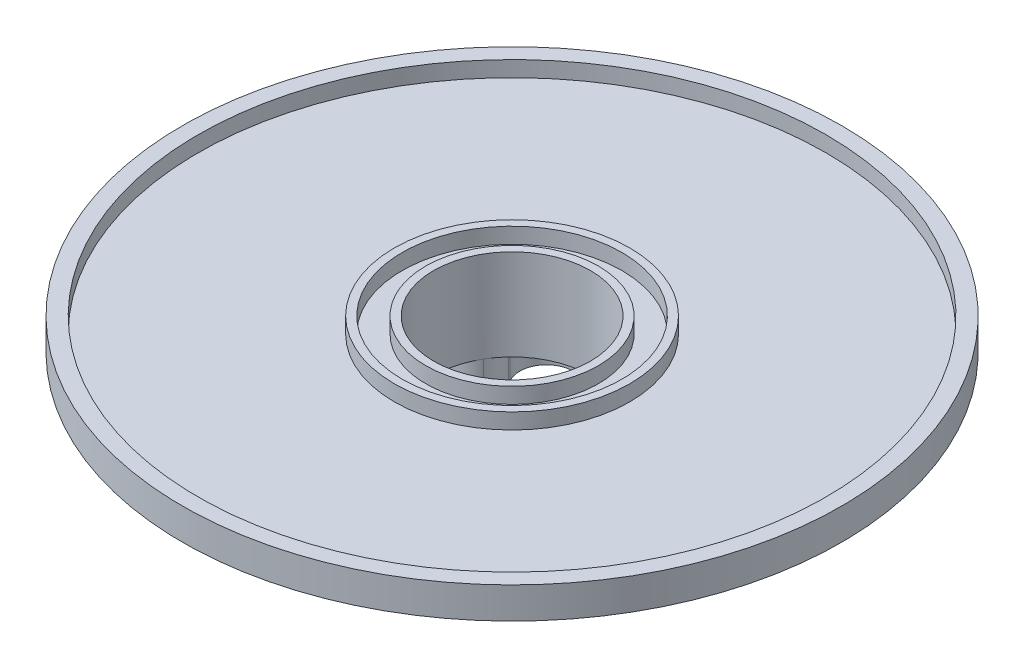
SolidWorks part; units mm, degrees
ref_plane "Front Plane" through (0, 0, 0) normal (0, 0, 1) x (1, 0, 0)
ref_plane "Top Plane" through (0, 0, 0) normal (0, 1, 0) x (1, 0, 0)
ref_plane "Right Plane" through (0, 0, 0) normal (1, 0, 0) x (0, 0, -1)
sketch "Sketch1" plane through (0, 0, 0) normal (0, 0, 1) x (1, 0, 0)
  line L0 (0, 0) -> (0, 80) construction
  line L1 (0, 0) -> (-50, 0)
  line L2 (-50, 0) -> (-50, 30)
  line L3 (-50, 30) -> (-105, 30)
  line L4 (-105, 30) -> (-105, 40)
  line L5 (-105, 40) -> (-100, 40)
  line L6 (-100, 40) -> (-100, 35)
  line L7 (-100, 35) -> (0, 35)
  line L8 (0, 0) -> (0, 35)
  dimension "D1" = 50
  dimension "D2" = 30
  dimension "D3" = 10
  dimension "D4" = 100
  dimension "D5" = 5
  dimension "D6" = 5
revolve "Revolve1" add sketch "Sketch1" angle 360 about L0
sketch "Sketch2" plane through (0, 0, 0) normal (0, -1, 0) x (1, 0, 0)
  line L0 (0, 0) -> (-30, 0) construction
  line L1 (-30, -7.5) -> (-22.798, -7.5) construction
  line L2 (-8.5048, 29.7308) -> (-4.9038, 23.4937) construction
  line L3 (-30, 7.5) -> (-22.798, 7.5) construction
  line L4 (-21.4952, 22.2308) -> (-17.8942, 15.9937) construction
  line L5 (21.4952, 22.2308) -> (17.8942, 15.9937) construction
  line L6 (8.5048, 29.7308) -> (4.9038, 23.4937) construction
  line L7 (30, -7.5) -> (22.798, -7.5) construction
  line L8 (30, 7.5) -> (22.798, 7.5) construction
  line L9 (8.5048, -29.7308) -> (4.9038, -23.4937) construction
  line L10 (21.4952, -22.2308) -> (17.8942, -15.9937) construction
  line L11 (-21.4952, -22.2308) -> (-17.8942, -15.9937) construction
  line L12 (-8.5048, -29.7308) -> (-4.9038, -23.4937) construction
  line L13 (0, 0) -> (-22.798, 7.5) construction
  line L14 (-22.3612, 21.7308) -> (-19.1165, 16.1108)
  line L15 (-30, 8.5) -> (-23.5106, 8.5)
  line L16 (-30, -8.5) -> (-23.5106, -8.5)
  line L17 (-22.3612, -21.7308) -> (-19.1165, -16.1108)
  line L18 (-7.6388, -30.2308) -> (-4.3941, -24.6108)
  line L19 (7.6388, -30.2308) -> (4.3941, -24.6108)
  line L20 (22.3612, -21.7308) -> (19.1165, -16.1108)
  line L21 (30, -8.5) -> (23.5106, -8.5)
  line L22 (30, 8.5) -> (23.5106, 8.5)
  line L23 (22.3612, 21.7308) -> (19.1165, 16.1108)
  line L24 (7.6388, 30.2308) -> (4.3941, 24.6108)
  line L25 (-7.6388, 30.2308) -> (-4.3941, 24.6108)
  arc A0 (-22.798, -7.5) -> (-17.8942, -15.9937) centre (0, 0) ccw construction
  arc A1 (-30, 7.5) -> (-30, -7.5) centre (-30, 0) ccw construction
  arc A2 (-8.5048, 29.7308) -> (-21.4952, 22.2308) centre (-15, 25.9808) ccw construction
  arc A3 (21.4952, 22.2308) -> (8.5048, 29.7308) centre (15, 25.9808) ccw construction
  arc A4 (30, -7.5) -> (30, 7.5) centre (30, 0) ccw construction
  arc A5 (8.5048, -29.7308) -> (21.4952, -22.2308) centre (15, -25.9808) ccw construction
  arc A6 (-21.4952, -22.2308) -> (-8.5048, -29.7308) centre (-15, -25.9808) ccw construction
  arc A7 (-17.8942, 15.9937) -> (-22.798, 7.5) centre (0, 0) ccw construction
  arc A8 (4.9038, 23.4937) -> (-4.9038, 23.4937) centre (0, 0) ccw construction
  arc A9 (22.798, 7.5) -> (17.8942, 15.9937) centre (0, 0) ccw construction
  arc A10 (17.8942, -15.9937) -> (22.798, -7.5) centre (0, 0) ccw construction
  arc A11 (-4.9038, -23.4937) -> (4.9038, -23.4937) centre (0, 0) ccw construction
  arc A12 (-7.6388, 30.2308) -> (-22.3612, 21.7308) centre (-15, 25.9808) ccw
  arc A13 (-19.1165, 16.1108) -> (-23.5106, 8.5) centre (0, 0) ccw
  arc A14 (-30, 8.5) -> (-30, -8.5) centre (-30, 0) ccw
  arc A15 (-23.5106, -8.5) -> (-19.1165, -16.1108) centre (0, 0) ccw
  arc A16 (-22.3612, -21.7308) -> (-7.6388, -30.2308) centre (-15, -25.9808) ccw
  arc A17 (-4.3941, -24.6108) -> (4.3941, -24.6108) centre (0, 0) ccw
  arc A18 (7.6388, -30.2308) -> (22.3612, -21.7308) centre (15, -25.9808) ccw
  arc A19 (19.1165, -16.1108) -> (23.5106, -8.5) centre (0, 0) ccw
  arc A20 (30, -8.5) -> (30, 8.5) centre (30, 0) ccw
  arc A21 (23.5106, 8.5) -> (19.1165, 16.1108) centre (0, 0) ccw
  arc A22 (22.3612, 21.7308) -> (7.6388, 30.2308) centre (15, 25.9808) ccw
  arc A23 (4.3941, 24.6108) -> (-4.3941, 24.6108) centre (0, 0) ccw
  dimension "D1" = 1
  dimension "D3" = 15
  dimension "D2" = 30
  dimension "D6" = 18.21
  dimension "D4" = 6
extrude "Cut-Extrude1" cut sketch "Sketch2" against normal blind 11
fillet "Fillet1" radius 8 12 edges at (23.5106, 5.5, -8.5) (19.1165, 5.5, -16.1108) (-4.3941, 5.5, -24.6108) (4.3941, 5.5, -24.6108) (-23.5106, 5.5, -8.5) (-19.1165, 5.5, -16.1108) (19.1165, 5.5, 16.1108) (23.5106, 5.5, 8.5) (4.3941, 5.5, 24.6108) (-4.3941, 5.5, 24.6108) (-23.5106, 5.5, 8.5) (-19.1165, 5.5, 16.1108)
sketch "Sketch3" plane through (0, 11, 0) normal (0, -1, 0) x (1, 0, 0)
  line L0 (0, 0) -> (-29.1531, 0) construction
  line L1 (0, 0) -> (-15, 25.9808) construction
  circle A0 centre (-15, 25.9808) radius 3
  circle A1 centre (15, 25.9808) radius 3
  circle A2 centre (30, 0) radius 3
  circle A3 centre (15, -25.9808) radius 3
  circle A4 centre (-15, -25.9808) radius 3
  circle A5 centre (-30, 0) radius 3
  dimension "D3" = 6
  dimension "D2" = 30
  dimension "D1" = 6
extrude "Cut-Extrude2" cut sketch "Sketch3" against normal blind 3
sketch "Sketch4" plane through (0, 0, 0) normal (0, -1, 0) x (1, 0, 0)
  line L1 (0, 0) -> (-50, 0) construction
  line L2 (0, 0) -> (-34.641, -20) construction
  circle A0 centre (-34.641, -20) radius 5
  circle A1 centre (0, 0) radius 50 construction
  circle A2 centre (-34.641, 20) radius 5
  circle A3 centre (0, 40) radius 5
  circle A4 centre (34.641, 20) radius 5
  circle A5 centre (34.641, -20) radius 5
  circle A6 centre (0, -40) radius 5
  dimension "D1" = 10
  dimension "D2" = 6
  dimension "D3" = 30
  dimension "D4" = 40
extrude "Cut-Extrude3" cut sketch "Sketch4" against normal blind 4.5
sketch "Sketch5" plane through (0, 11, 0) normal (0, -1, 0) x (1, 0, 0)
  circle A0 centre (0, 0) radius 25
  dimension "D1" = 50
extrude "Cut-Extrude4" cut sketch "Sketch5" against normal through all
sketch "Sketch6" plane through (0, 35, 0) normal (0, 1, 0) x (1, 0, 0)
  circle A0 centre (0, 0) radius 27.5
  circle A1 centre (0, 0) radius 25
  circle A2 centre (0, 0) radius 25 construction
  circle A3 centre (0, 0) radius 35
  circle A4 centre (0, 0) radius 37.5
  circle M1 centre (0, 0) radius 25
  dimension "D1" = 55
  dimension "D2" = 75
  dimension "D3" = 70
extrude "Boss-Extrude1" add sketch "Sketch6" along normal blind 5 contours A0 M1 | A4 A3 region at (-26.7222, 35, 0) region at (-36.4393, 35, 0)
sketch "Sketch8" plane through (0, 0, 0) normal (0, -1, 0) x (1, 0, 0)
  line L0 (0, 11.8041) -> (0, 0) construction
  line L1 (-7.5, 11.8041) -> (7.5, 11.8041)
  line L2 (-7.5, 11.8041) -> (-7.5, 60.3613)
  line L3 (-7.5, 60.3613) -> (7.5, 60.3613)
  line L4 (7.5, 11.8041) -> (7.5, 60.3613)
  dimension "D1" = 15
extrude "Cut-Extrude5" cut sketch "Sketch8" against normal up to surface (30 mm away) up to face at (0, 30, -50)
